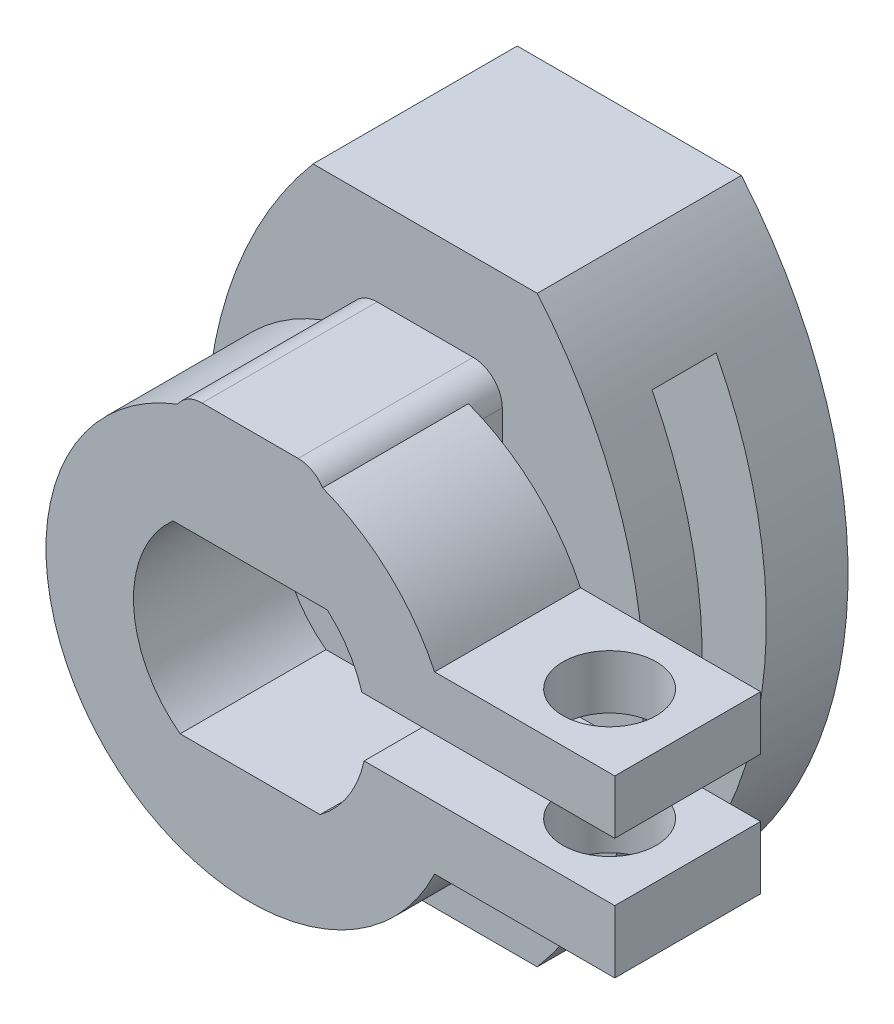
SolidWorks part; units mm, degrees
ref_plane "前视基准面" through (0, 0, 0) normal (0, 0, 1) x (1, 0, 0)
ref_plane "上视基准面" through (0, 0, 0) normal (0, 1, 0) x (1, 0, 0)
ref_plane "右视基准面" through (0, 0, 0) normal (1, 0, 0) x (0, 0, -1)
sketch "草图1" plane through (0, 0, 0) normal (0, 0, 1) x (1, 0, 0)
  line L1 (-8, -10) -> (8, -10)
  line L2 (-8, -10) -> (-8, 10)
  line L3 (-8, 10) -> (8, 10)
  line L4 (8, -10) -> (8, 10)
  line L5 (-8, -10) -> (8, 10) construction
  line L6 (-8, 10) -> (8, -10) construction
  point P0 (0, 0)
extrude "凸台-拉伸1" add sketch "草图1" along normal blind 7
sketch "草图2" plane through (0, 0, 7) normal (0, 0, 1) x (1, 0, 0)
  line L0 (-2.6458, 3) -> (2.6458, 3)
  line L1 (-2.6957, -3.2) -> (2.6957, -3.2)
  arc A0 (2.6458, 3) -> (2.6957, -3.2) centre (0, -0.1215) cw
  arc A1 (-2.6458, 3) -> (-2.6957, -3.2) centre (0, -0.1215) ccw
  point P1 (0, 0)
  point P4 (0, 0)
  point P6 (0, 0)
  point P7 (0, 0)
  point P8 (0, 3)
  point P11 (0, -3.2)
extrude "切除-拉伸1" cut sketch "草图2" against normal blind 15
sketch "草图4" plane through (0, 0, 7) normal (0, 0, 1) x (1, 0, 0)
  line L0 (8, -10) -> (8, 10) construction
  line L1 (8, 10) -> (-8, 10) construction
  line L2 (-8, -10) -> (8, -10) construction
  line L3 (-8, 10) -> (-8, -10) construction
  line L4 (-3.8427, 10) -> (-8, 10)
  line L5 (-8, 10) -> (-8, -10)
  line L6 (-8, -10) -> (-3.8427, -10)
  line L7 (3.8427, 10) -> (8, 10)
  line L8 (8, 10) -> (8, -10)
  line L9 (8, -10) -> (3.8427, -10)
  arc A0 (-3.8427, 10) -> (-3.8427, -10) centre (8, 0) ccw
  arc A1 (3.8427, 10) -> (3.8427, -10) centre (-8, 0) cw
extrude "切除-拉伸3" cut sketch "草图4" against normal through all
sketch "草图6" plane through (0, 0, 7) normal (0, 0, 1) x (1, 0, 0)
  line L0 (-2.6458, 3) -> (2.6458, 3)
  line L1 (2.6458, 3) -> (2.6458, 7)
  line L2 (2.6458, 7) -> (-2.6458, 7)
  line L3 (-2.6458, 7) -> (-2.6458, 3)
  point P6 (0, 0)
  point P7 (0, 0)
extrude "凸台-拉伸2" add sketch "草图6" along normal blind 1
sketch "草图7" plane through (-2.6458, 0, 0) normal (-1, 0, 0) x (0, 0, 1)
  line L2 (5, -7.1) -> (5, 7.1)
  line L3 (5, 7.1) -> (2.8, 7.1)
  line L4 (2.8, 7.1) -> (2.8, -7.1)
  line L5 (2.8, -7.1) -> (5, -7.1)
  point P9 (5, 0)
extrude "切除-拉伸5" cut sketch "草图7" against normal through all both and the other way through all
sketch "草图8" plane through (0, 0, 0) normal (0, 0, -1) x (-1, 0, 0)
  circle A0 centre (0, 0) radius 4.915
extrude "凸台-拉伸3" add sketch "草图8" against normal blind 1.5
sketch "草图9" plane through (0, 0, 8) normal (0, 0, 1) x (1, 0, 0)
  circle A2 centre (0, 0) radius 4
  circle A3 centre (0, 0) radius 7
extrude "凸台-拉伸4" add sketch "草图9" along normal blind 5
sketch "草图10" plane through (0, 0, 8) normal (0, 0, 1) x (1, 0, 0)
  line L0 (-2.6957, -3.2) -> (2.6957, -3.2) construction
  line L1 (-2.6458, 3) -> (2.6458, 3)
  line L2 (-2.6458, 3) -> (-2.6458, 7)
  line L3 (-2.6458, 7) -> (2.6458, 7)
  line L4 (2.6458, 3) -> (2.6458, 7)
  line L5 (-2.6458, -3.2) -> (2.6957, -3.2)
  line L6 (-2.6458, -3.2) -> (-2.6458, -5.0944)
  line L7 (-2.6458, -5.0944) -> (2.6957, -5.0944)
  line L8 (2.6957, -3.2) -> (2.6957, -5.0944)
extrude "凸台-拉伸5" add sketch "草图10" along normal blind 5
fillet "圆角1" radius 1 2 edges at (2.6458, 7, 10) (-2.6458, 7, 10)
sketch "草图11" plane through (0, 0, 13) normal (0, 0, 1) x (1, 0, 0)
  line L3 (12.5016, 1) -> (12.5016, -1)
  line L6 (5.4008, 1) -> (5.4008, -1)
  line L7 (5.4008, 1) -> (5.4008, 3)
  line L8 (5.4008, 3) -> (12.5016, 3)
  line L9 (12.5016, 3) -> (12.5016, 1)
  line L10 (12.5016, -1) -> (12.5016, -3)
  line L11 (12.5016, -3) -> (5.4008, -3)
  line L12 (5.4008, -3) -> (5.4008, -1)
  point P4 (0, 0)
extrude "凸台-拉伸6" add sketch "草图11" against normal blind 5
sketch "草图12" plane through (0, 0, 13) normal (0, 0, 1) x (1, 0, 0)
  line L0 (12.5016, -0.8517) -> (12.5016, 1.1483)
  line L1 (12.5016, -3) -> (12.5016, 3) construction
  line L2 (12.5016, 1.1483) -> (1.6033, 1.1483)
  line L3 (1.6033, 1.1483) -> (1.6033, -0.8517)
  line L4 (1.6033, -0.8517) -> (12.5016, -0.8517)
  point P5 (12.5016, 0.1483)
extrude "切除-拉伸6" cut sketch "草图12" against normal blind 5 and the other way through all
sketch "草图13" plane through (0, 3, 0) normal (0, 1, 0) x (1, 0, 0)
  circle A0 centre (9.8246, -10.5) radius 1.6
extrude "切除-拉伸7" cut sketch "草图13" against normal through all
